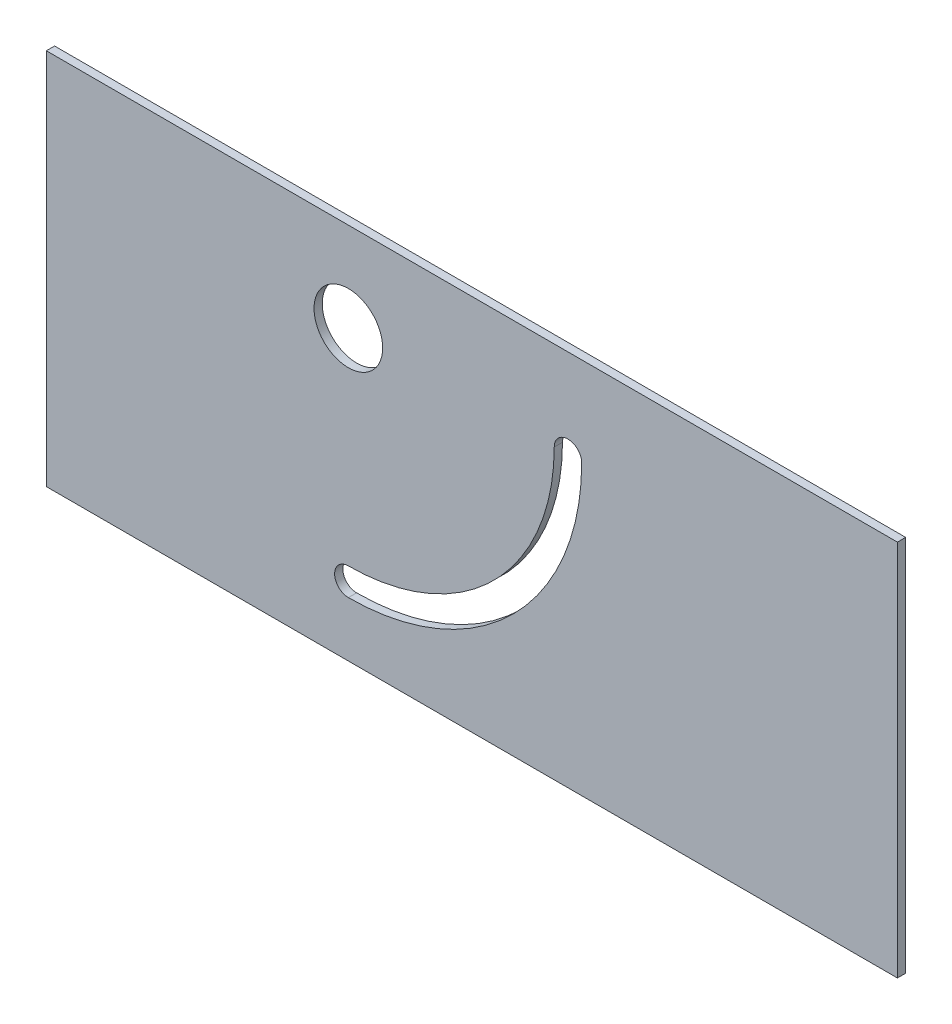
SolidWorks part; units mm, degrees
ref_plane "Front Plane" through (0, 0, 0) normal (0, 0, 1) x (1, 0, 0)
ref_plane "Top Plane" through (0, 0, 0) normal (0, 1, 0) x (1, 0, 0)
ref_plane "Right Plane" through (0, 0, 0) normal (1, 0, 0) x (0, 0, -1)
sketch "Sketch1" plane through (0, 0, 32.5) normal (0, 0, 1) x (1, 0, 0)
  line L1 (-25.5, 128.5) -> (284.5, 128.5)
  line L2 (-25.5, 128.5) -> (-25.5, -9)
  line L3 (-25.5, -9) -> (284.5, -9)
  line L4 (284.5, 128.5) -> (284.5, -9)
  line L5 (84.5, 59.75) -> (84.5, -77.75) construction
  circle A1 centre (84.5, 96) radius 12.5 construction
  arc A3 (169.5, 96) -> (159.5, 96) centre (164.5, 96) ccw
  arc A4 (159.5, 96) -> (84.5, 21) centre (84.5, 96) cw
  arc A5 (169.5, 96) -> (84.5, 11) centre (84.5, 96) cw
  arc A6 (84.5, 11) -> (84.5, 21) centre (84.5, 16) cw
  circle A7 centre (84.5, 96) radius 12.5
  point P7 (198.2412, -10.3422)
  point P8 (-16.7116, 133.5242)
  point P10 (0, 0)
  point P11 (84.5, 20.9998)
  point P17 (-6.9064, 130.4198)
  point P20 (0, 0)
  point P21 (338, 135.1346)
  point P22 (265.3185, -65.6819)
  point P23 (268.506, 126.2701)
  point P25 (0, 0)
  point P26 (0, 0)
  point P27 (0, 0)
  point P28 (0, 0)
  point P29 (0, 0)
  point P30 (0, 0)
  point P31 (0, 0)
  point P32 (0, 0)
  point P33 (0, 0)
  point P34 (0, 0)
  point P35 (169.5, 102.1294)
  point P36 (0, 0)
  dimension "D1" = 10
  dimension "D2" = 75
  dimension "D3" = 20
  dimension "D4" = 20
  dimension "D5" = 110
  dimension "D6" = 200
extrude "Boss-Extrude1" add sketch "Sketch1" along normal blind 3
